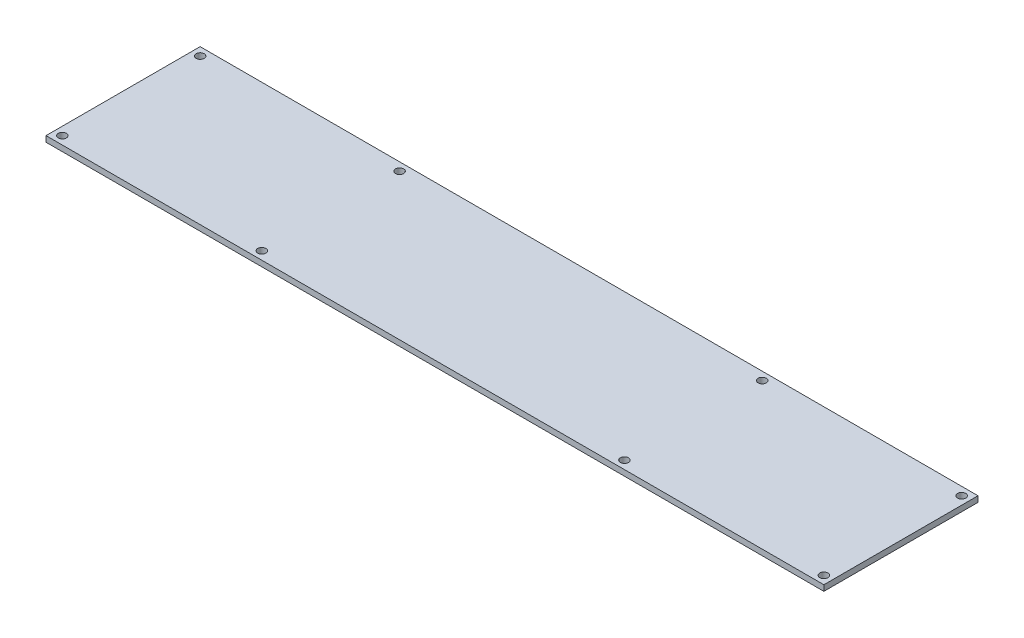
SolidWorks part; units mm, degrees
ref_plane "Front Plane" through (0, 0, 0) normal (0, 0, 1) x (1, 0, 0)
ref_plane "Top Plane" through (0, 0, 0) normal (0, 1, 0) x (1, 0, 0)
ref_plane "Right Plane" through (0, 0, 0) normal (1, 0, 0) x (0, 0, -1)
sketch "Sketch1" plane through (0, 0, 0) normal (0, 1, 0) x (1, 0, 0)
  line L1 (-214.5, -42.5) -> (214.5, -42.5)
  line L2 (-214.5, -42.5) -> (-214.5, 42.5)
  line L3 (-214.5, 42.5) -> (214.5, 42.5)
  line L4 (214.5, -42.5) -> (214.5, 42.5)
  line L5 (-214.5, -42.5) -> (214.5, 42.5) construction
  line L6 (-214.5, 42.5) -> (214.5, -42.5) construction
  point P0 (0, 0)
  dimension "D1" = 429
  dimension "D2" = 85
extrude "Boss-Extrude1" add sketch "Sketch1" along normal blind 3.175
hole_wizard "M4 Clearance Hole1" positions "Sketch2" profile "Sketch3" hole size "M4" standard "ANSI Metric" end condition through all
sketch "Sketch2" plane through (0, 3.175, 0) normal (0, 1, 0) x (1, 0, 0)
  line L0 (214.5, 42.5) -> (-214.5, 42.5) construction
  line L1 (-214.5, 42.5) -> (-214.5, -42.5) construction
  line L2 (0, -55) -> (0, 55) construction
  line L4 (-100, 38) -> (100, 38)
  line L5 (-55, 0) -> (55, 0) construction
  line L6 (-100, -38) -> (100, -38)
  point P0 (-210, 38)
  point P9 (210, 38)
  point P12 (-100, 38)
  point P13 (100, 38)
  point P21 (0, 38)
  point P27 (100, -38)
  point P28 (-100, -38)
  point P29 (210, -38)
  point P30 (-210, -38)
  dimension "D1" = 4.5
  dimension "D2" = 4.5
  dimension "D3" = 200
sketch "Sketch3" plane through (-210, 3.175, -38) normal (1, 0, 0) x (0, 0, 1)
  line L0 (0, 0) -> (0, 3.175)
  line L1 (0, 3.175) -> (2.25, 3.175)
  line L2 (2.25, 3.175) -> (2.25, 0)
  line L5 (2.25, 0) -> (0, 0)
  line L11 (0, -6.35) -> (0, 107.95) construction
  dimension "Thru Hole Dia." = 4.5
  dimension "Thru Hole Depth" = 3.175
